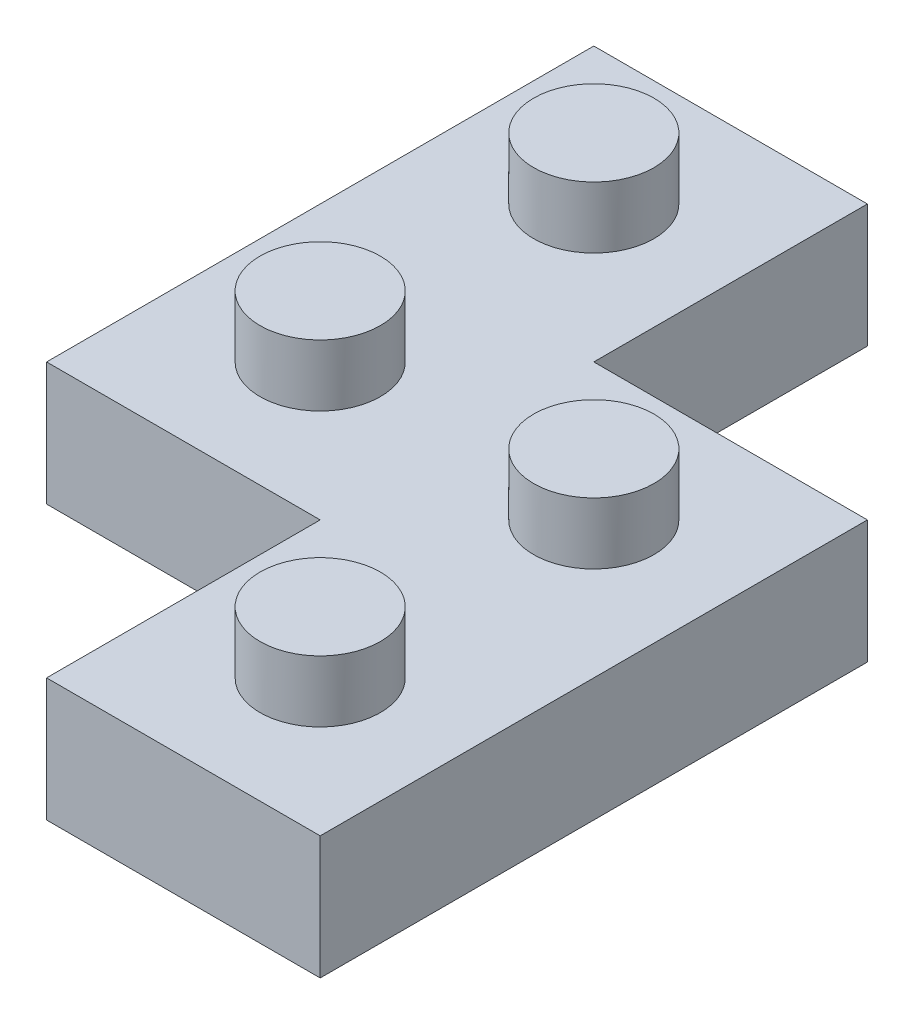
SolidWorks part; units mm, degrees
ref_plane "Front Plane" through (0, 0, 0) normal (0, 0, 1) x (1, 0, 0)
ref_plane "Top Plane" through (0, 0, 0) normal (0, 1, 0) x (1, 0, 0)
ref_plane "Right Plane" through (0, 0, 0) normal (1, 0, 0) x (0, 0, -1)
sketch "Sketch1" plane through (0, 0, 0) normal (0, 1, 0) x (1, 0, 0)
  line L0 (-5.6746, 20.3112) -> (7.0254, 20.3112)
  line L1 (7.0254, 20.3112) -> (7.0254, 7.6112)
  line L2 (7.0254, 7.6112) -> (19.7254, 7.6112)
  line L3 (19.7254, 7.6112) -> (19.7254, -17.7888)
  line L4 (19.7254, -17.7888) -> (7.0254, -17.7888)
  line L5 (7.0254, -17.7888) -> (7.0254, -5.0888)
  line L6 (7.0254, -5.0888) -> (-5.6746, -5.0888)
  line L7 (-5.6746, -5.0888) -> (-5.6746, 20.3112)
  point P9 (0, 0)
  point P10 (22.5752, 7.1658)
  point P11 (0, 0)
  dimension "D1" = 38.1
  dimension "D2" = 12.7
  dimension "D3" = 12.7
  dimension "D4" = 12.7
  dimension "D5" = 12.7
extrude "Boss-Extrude1" add sketch "Sketch1" along normal blind 5.715
sketch "Sketch2" plane through (0, 5.715, 0) normal (0, 1, 0) x (1, 0, 0)
  line L0 (-5.6746, 20.3112) -> (-5.6746, -5.0888) construction
  line L1 (19.7254, -17.7888) -> (19.7254, 7.6112) construction
  line L2 (7.0254, 20.3112) -> (-5.6746, 20.3112) construction
  circle A0 centre (0.6754, 1.2612) radius 2.794
  circle A1 centre (13.3754, 1.2612) radius 2.794
  circle A2 centre (0.6754, 13.9612) radius 2.794
  circle A3 centre (13.3754, -11.4388) radius 2.794
  point P14 (0, 0)
  point P15 (0, 0)
  point P16 (0, 0)
  dimension "D2" = 6.35
  dimension "D4" = 6.35
  dimension "D5" = 12.7
  dimension "D3" = 6.35
  dimension "D6" = 12.7
  dimension "D1" = 2
extrude "Boss-Extrude3" add sketch "Sketch2" along normal blind 2.8575
